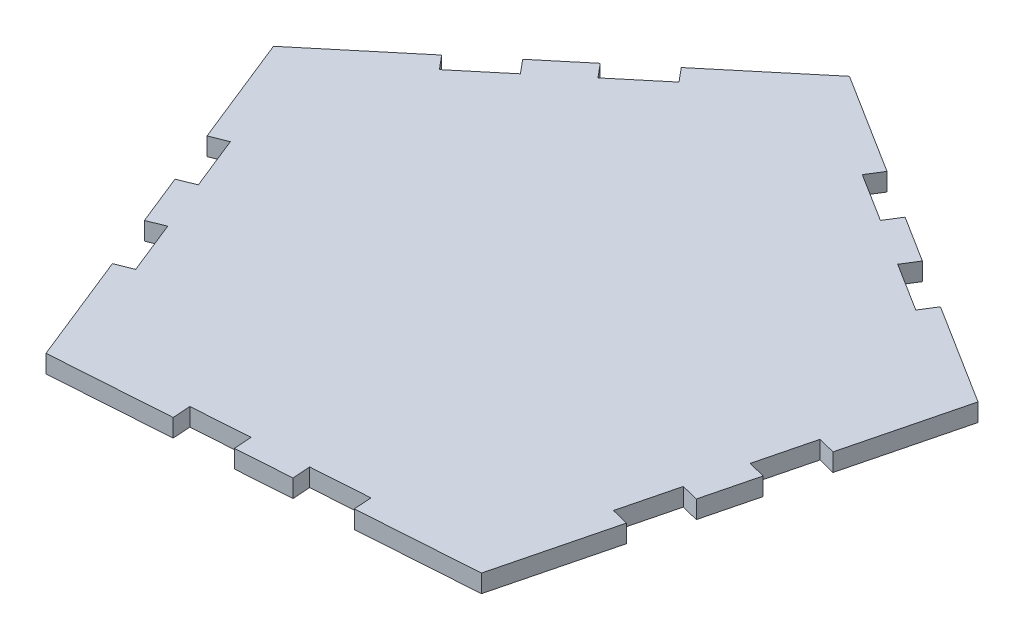
SolidWorks part; units mm, degrees
ref_plane "Front Plane" through (0, 0, 0) normal (0, 0, 1) x (1, 0, 0)
ref_plane "Top Plane" through (0, 0, 0) normal (0, 1, 0) x (1, 0, 0)
ref_plane "Right Plane" through (0, 0, 0) normal (1, 0, 0) x (0, 0, -1)
sketch "Sketch1" plane through (0, 0, 0) normal (0, 1, 0) x (1, 0, 0)
  line L1 (-59.9258, 15.1181) -> (-32.8962, -52.3211)
  line L2 (-32.8962, -52.3211) -> (39.5948, -47.4543)
  line L3 (39.5948, -47.4543) -> (57.3672, 22.9927)
  line L4 (57.3672, 22.9927) -> (-4.14, 61.6646)
  line L5 (-4.14, 61.6646) -> (-59.9258, 15.1181)
  circle A0 centre (0, 0) radius 50 construction
  dimension "D1" = 100
extrude "Boss-Extrude1" add sketch "Sketch1" along normal blind 3.18
sketch "Sketch2" plane through (0, 0, 0) normal (0, -1, 0) x (1, 0, 0)
  line L0 (-52.0324, 4.5761) -> (-49.0807, 3.3931)
  line L1 (-52.0324, 4.5761) -> (-48.2303, 14.0625)
  line L2 (-49.0807, 3.3931) -> (-45.2785, 12.8795)
  line L3 (-48.2303, 14.0625) -> (-45.2785, 12.8795)
  line L4 (-59.9258, -15.1181) -> (-32.8962, 52.3211) construction
  line L5 (-44.5918, 23.1405) -> (-40.7896, 32.6269)
  line L6 (-44.5918, 23.1405) -> (-41.6401, 21.9575)
  line L7 (-40.7896, 32.6269) -> (-37.8379, 31.4439)
  line L8 (-41.6401, 21.9575) -> (-37.8379, 31.4439)
  line L9 (-46.411, 18.6015) -> (-19.2439, 7.7129) construction
  dimension "D1" = 3.18
extrude "Cut-Extrude1" cut sketch "Sketch2" against normal through all
ref_axis "Axis1" through (0, 3.339, 0) along (0, -1, 0)
pattern_circular "CirPattern1" count 5 over 360 about axis through (0, 3.339, 0) along (0, -1, 0) of "Cut-Extrude1"
equation "\"kerf\"= .22mm"
equation "\"amountofcuts\" = 3"
equation "\"tabWidth\"= 10 + \"kerf\" "
equation "\"tabSeperation\" = 10 - \"kerf\" "
equation "\"tabThickness\"= 3.18"
equation "\"D2@Sketch2\"=\"tabWidth\""
equation "\"D3@Sketch2\"=\"tabSeperation\""
equation "\"D1@Sketch2\"=\"tabThickness\""
equation "\"tabLength\" = \"kerf\" + 12"
